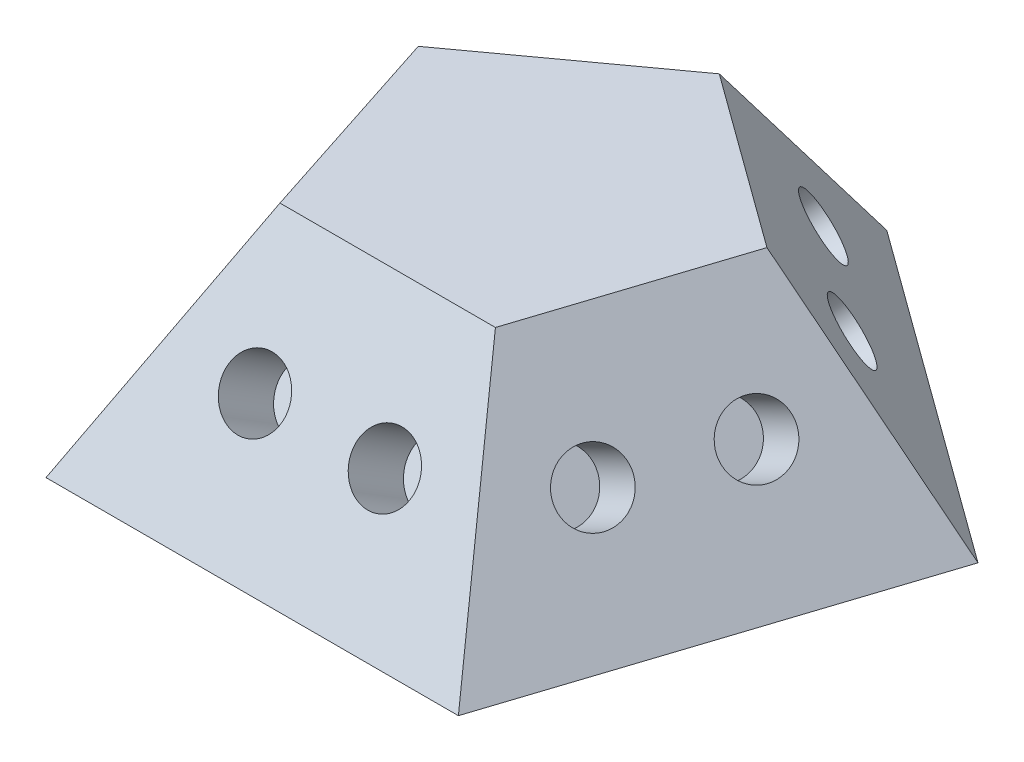
SolidWorks part; units mm, degrees
ref_plane "Front Plane" through (0, 0, 0) normal (0, 0, 1) x (1, 0, 0)
ref_plane "Top Plane" through (0, 0, 0) normal (0, 1, 0) x (1, 0, 0)
ref_plane "Right Plane" through (0, 0, 0) normal (1, 0, 0) x (0, 0, -1)
ref_axis "Axis1" through (0, 14.8487, 0) along (0, -1, 0)
sketch "Sketch1" plane through (0, 0, 0) normal (0, 1, 0) x (1, 0, 0)
  line L1 (0, 10.8033) -> (-10.2745, 3.3384)
  line L2 (-10.2745, 3.3384) -> (-6.35, -8.74)
  line L3 (-6.35, -8.74) -> (6.35, -8.74)
  line L4 (6.35, -8.74) -> (10.2745, 3.3384)
  line L5 (10.2745, 3.3384) -> (0, 10.8033)
  circle A0 centre (0, 0) radius 8.74 construction
  dimension "D1" = 12.7
extrude "Boss-Extrude1" add sketch "Sketch1" along normal blind 25.4 draft 31.717
mirror "Mirror1" [suppressed]
sketch "Sketch3" plane through (0, 3.9087, 6.3243) normal (0, 0.5257, 0.8507) x (1, 0, 0)
  line L0 (-2, -0.6262) -> (2, -0.6262) construction
  line L1 (-6.35, -4.5949) -> (6.35, -4.5949) construction
  line L2 (-2, -4.5949) -> (-2, 3.3426) construction
  circle A0 centre (-2, -0.6262) radius 1
  circle A1 centre (2, -0.6262) radius 1
  point P4 (0, -0.6262)
  point P5 (-2, -0.6262)
  dimension "D1" = 2
  dimension "D2" = 4
  dimension "D3" = 3.9688
extrude "Cut-Extrude1" cut sketch "Sketch3" against normal blind 2
pattern_circular "CirPattern1" count 5 over 360 about axis through (0, 14.8487, 0) along (0, -1, 0) of "Cut-Extrude1"
sketch "Sketch4" plane through (0, 0, 0) normal (0, -1, 0) x (1, 0, 0)
  line L5 (0, -10.8033) -> (10.2745, -3.3384)
  line L6 (10.2745, -3.3384) -> (6.35, 8.74)
  line L7 (6.35, 8.74) -> (-6.35, 8.74)
  line L8 (-6.35, 8.74) -> (-10.2745, -3.3384)
  line L9 (-10.2745, -3.3384) -> (0, -10.8033)
  line L10 (0, -10.8033) -> (10.2745, -3.3384)
  line L11 (10.2745, -3.3384) -> (6.35, 8.74)
  line L12 (6.35, 8.74) -> (-6.35, 8.74)
  line L13 (-6.35, 8.74) -> (-10.2745, -3.3384)
  line L14 (-10.2745, -3.3384) -> (0, -10.8033)
  dimension "D1" = 0
extrude "Cut-Extrude2" cut sketch "Sketch4" against normal through all from vertex starting at point (-2, 6.752, 4.567)
equation "\"angle\"= arccos ( - sqr ( 5 ) / 5 )"
equation "\"theta\"= 90 - \"angle\" / 2"
equation "\"side\"=0.5"
equation "\"D1@Sketch1\"=\"side\""
equation "\"D3@Boss-Extrude1\"=\"theta\""
equation "\"D1@Boss-Extrude1\"=\"side\"*2"
